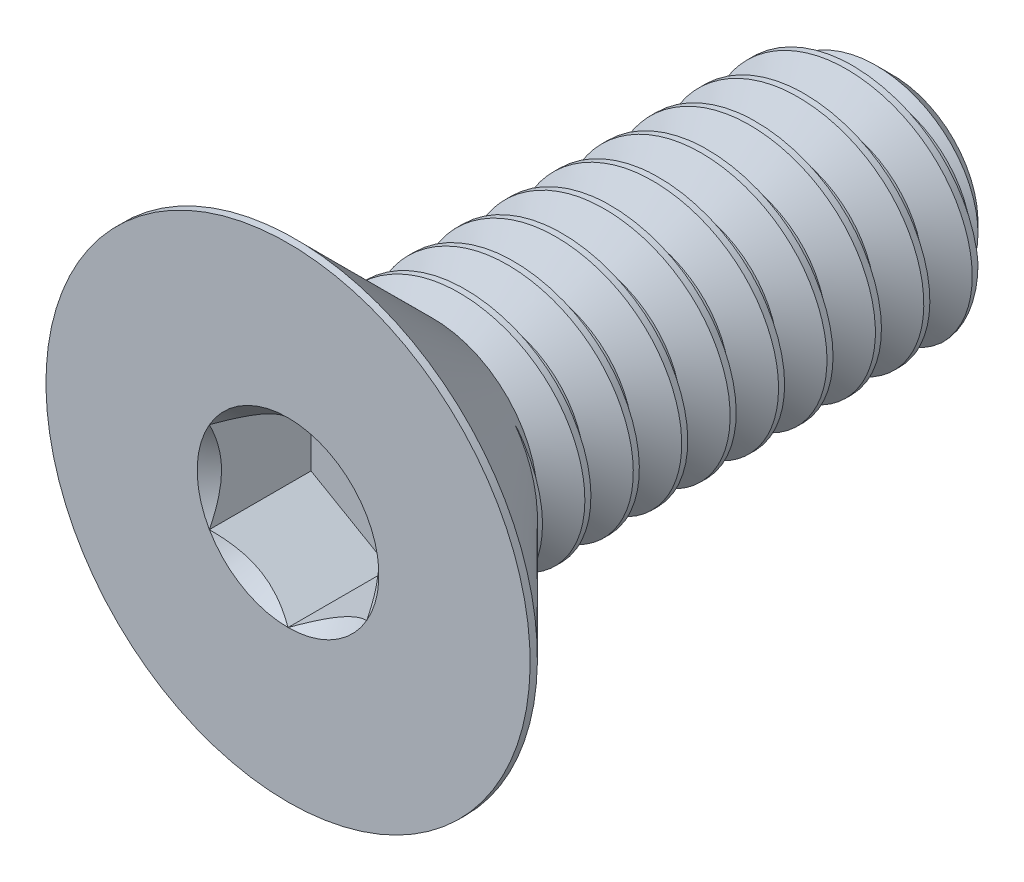
SolidWorks part; units mm, degrees
ref_plane "Front" through (0, 0, 0) normal (0, 0, 1) x (1, 0, 0)
ref_plane "Top" through (0, 0, 0) normal (0, 1, 0) x (1, 0, 0)
ref_plane "Right" through (0, 0, 0) normal (1, 0, 0) x (0, 0, -1)
sketch "Sketch11" plane through (0, 0, 0) normal (1, 0, 0) x (0, 0, -1)
  line L0 (-2.5, 2) -> (2.5, 2) construction
  line L5 (-2.5, 2) -> (-2.5, -2) construction
  line L6 (2.5, 1) -> (2.5, -1) construction
  line L7 (-2.49, 0.65) -> (-2.49, -0.65) construction
  line L8 (2.475, 1.0433) -> (2.875, 1.0433) construction
  line L9 (2.875, 1.0433) -> (2.675, 0.6969) construction
  line L10 (2.675, 0.6969) -> (2.475, 1.0433) construction
  line L11 (2.65, 0.7402) -> (2.7, 0.7402) construction
  line L12 (2.675, 0.7402) -> (2.675, 0.6969) construction
  line L13 (2.4875, 1.0217) -> (2.8625, 1.0217) construction
  line L14 (2.675, 1.0433) -> (2.675, 1) construction
  line L15 (2.5, 1) -> (2.85, 1) construction
  line L17 (-2.44, 2) -> (-0.44, 0) construction
  line L18 (-0.44, 0) -> (-2.44, -2) construction
  point P3 (-1.3, 2)
  point P8 (0, 2)
  point P21 (2.675, 1.0217)
  point P26 (-2.5, 0)
  point P28 (-2.49, 0)
  point P29 (2.5, 0)
  dimension "Length" = 5
  dimension "Head Diameter" = 4
  dimension "Thread Major Diameter" = 2
  dimension "Head Height" = 1.2
  dimension "Drive Size" = 1.3
  dimension "Thread Pitch" = 0.4
  dimension "D1" = 0.05
  dimension "D2" = 0.01
  dimension "D3" = 0.06
  dimension "Countersink Angle" = 90
sketch "Sketch1" plane through (0, 0, 0) normal (1, 0, 0) x (0, 0, -1)
  line L2 (-1.3, 1) -> (2.5, 1)
  line L3 (2.5, 1) -> (2.5, 0)
  line L4 (-1.66, 1) -> (-1.66, 0)
  line L5 (-1.3, 1) -> (-1.66, 1)
  line L6 (-2.5, 2) -> (-2.5, -2) construction
  line L7 (2.5, 1) -> (2.5, -1) construction
  line L8 (-1.66, 0) -> (2.5, 0)
  dimension "D1" = 0.84
revolve "Revolve1" add sketch "Sketch1" angle 360 mid plane about L8
chamfer "Chamfer1" distance 0.3 angle 45 1 edges at (0, -1, -2.5)
sketch "Sketch7" plane through (0, 0, 0) normal (1, 0, 0) x (0, 0, -1)
  line L2 (-2.5, 2) -> (-2.44, 2)
  line L5 (-1.3, 0.86) -> (-1.3, 0)
  line L6 (-2.5, 2) -> (-2.5, 0)
  line L8 (-2.5, 2) -> (-2.5, -2) construction
  line L9 (-2.5, 0) -> (-1.3, 0)
  line L12 (-2.44, 2) -> (-1.3, 0.86)
  line L13 (-2.44, 2) -> (-0.44, 0) construction
revolve "Revolve2" add sketch "Sketch7" angle 360 mid plane about L9 region at (0, 0.7698, 1.9817)
ref_plane "Plane1" through (0, 0, 1.3) normal (0, 0, 1) x (1, 0, 0)
sketch "Sketch5" plane through (0, 0, 2.5) normal (0, 0, 1) x (1, 0, 0)
  line L1 (0.65, -0.3753) -> (0.65, 0.3753)
  line L2 (0.65, 0.3753) -> (0, 0.7506)
  line L3 (0, 0.7506) -> (-0.65, 0.3753)
  line L4 (-0.65, 0.3753) -> (-0.65, -0.3753)
  line L5 (-0.65, -0.3753) -> (0, -0.7506)
  line L6 (0, -0.7506) -> (0.65, -0.3753)
  circle A0 centre (0, 0) radius 0.65 construction
extrude "Cut-Extrude2" cut sketch "Sketch5" against normal blind 0.84
sketch "Sketch6" plane through (0, 0, 2.5) normal (0, 0, -1) x (-1, 0, 0)
  circle A0 centre (0, 0) radius 0.7506
extrude "Cut-Extrude3" cut sketch "Sketch6" along normal blind 0.84 draft 45
sketch "Sketch12" plane through (0, 0, -2.5) normal (0, 0, -1) x (-1, 0, 0)
  circle A0 centre (0, 0) radius 1 construction
  circle A1 centre (0, 0) radius 1
curve "Helix/Spiral1" pitch 0.4 height 5 radius 1 centre (0, 0, -2.5) axis (0, 0, 1) start towards (0, 1, 0)
sketch "Sketch13" plane through (0, 0, 0) normal (1, 0, 0) x (0, 0, -1)
  line L0 (2.4875, 1.0217) -> (2.8625, 1.0217)
  line L1 (2.8625, 1.0217) -> (2.7, 0.7402)
  line L2 (2.7, 0.7402) -> (2.65, 0.7402)
  line L3 (2.65, 0.7402) -> (2.4875, 1.0217)
sweep "Cut-Sweep1" cut profiles "Sketch13" path "Helix/Spiral1" align with end faces yes
combine bodies "Combine1" operation type add bodies to combine 113 127
equation "\"D1@Chamfer1\"=\"Thread Pitch@Sketch11\" * .75"
equation "\"D1@Cut-Extrude2\"= \"Head Height@Sketch11\" * .7"
equation "\"D1@Cut-Extrude3\" = \"D1@Cut-Extrude2\""
equation "\"D1@Sketch11\"=\"Thread Pitch@Sketch11\"/8"
equation "\"D3@Sketch11\"=\"Head Height@Sketch11\"*.05"
equation "\"D4@Helix/Spiral1\"=\"Thread Pitch@Sketch11\""
equation "\"D1@Sketch1\"=\"Head Height@Sketch11\"*.7"
equation "\"D3@Helix/Spiral1\"=\"Length@Sketch11\""
